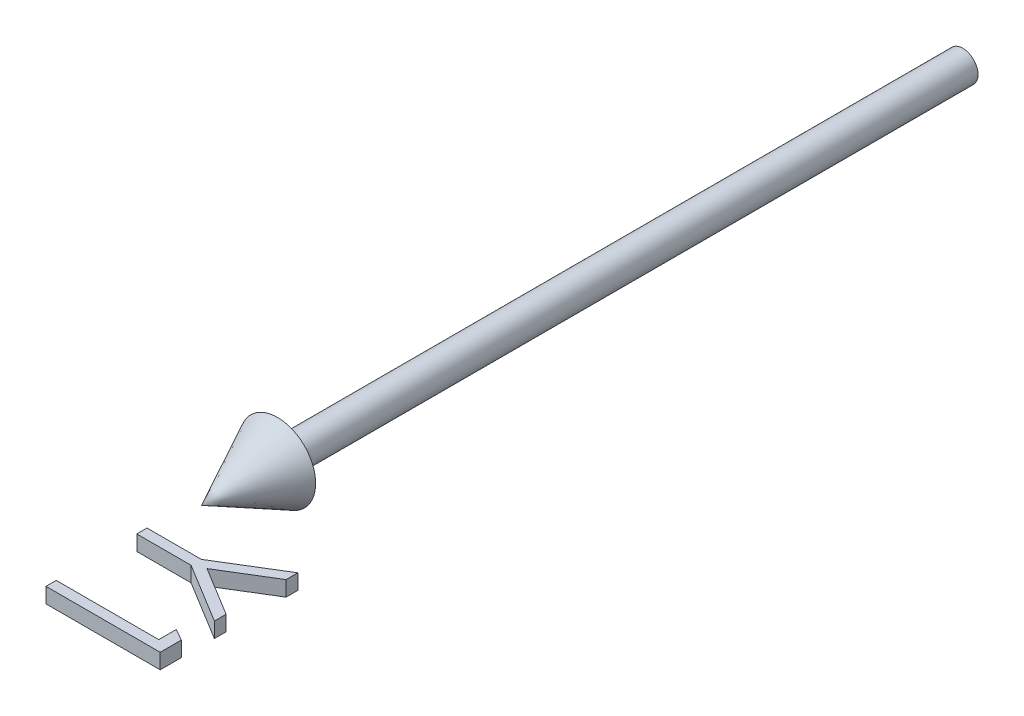
SolidWorks part; units mm, degrees
ref_plane "Front Plane" through (0, 0, 0) normal (0, 0, 1) x (1, 0, 0)
ref_plane "Top Plane" through (0, 0, 0) normal (0, 1, 0) x (1, 0, 0)
ref_plane "Right Plane" through (0, 0, 0) normal (1, 0, 0) x (0, 0, -1)
sketch "Sketch2" plane through (0, 0, 0) normal (0, 1, 0) x (1, 0, 0)
  line L0 (0, 41.95) -> (0, -114.4521) construction
  line L1 (-36.8894, 0) -> (41.4965, 0) construction
  line L2 (0, -100) -> (5, -90)
  line L3 (5, -90) -> (2, -90)
  line L4 (2, -90) -> (2, 0)
  line L5 (2, 0) -> (0, 0)
  line L6 (0, 0) -> (0, -100)
  dimension "D1" = 100
  dimension "D2" = 2
  dimension "D3" = 10
  dimension "D4" = 5
revolve "Revolve1" add sketch "Sketch2" angle 360 about L0
sketch "Sketch3" plane through (0, 0, 0) normal (0, 1, 0) x (1, 0, 0)
  line L0 (0, -101.5706) -> (0, -127.8138) construction
  text T0 "Y1" font "Century Gothic" height 15
extrude "Boss-Extrude1" add sketch "Sketch3" against normal blind 1 and the other way blind 1 separate body
equation "\"frame_arrow_length\"=100"
equation "\"D1@Sketch2\"=\"frame_arrow_length\""
equation "\"frame_arrow_odA\"=4"
equation "\"D2@Sketch2\"=\"frame_arrow_odA\"/2"
equation "\"frame_arrow_head_od\"=5"
equation "\"D4@Sketch2\"=\"frame_arrow_head_od\""
equation "\"frame_arrow_head_length\"=10"
equation "\"D3@Sketch2\"=\"frame_arrow_head_length\""
equation "\"tvarobot_theta1\"=30"
equation "\"link0_ringA_odA\"= 40"
equation "\"link0_ringA_odB\"= 25"
equation "\"link0_ringA_id\"= 20"
equation "\"link0_ringA_thickness\"= (\"link0_ringA_odB\" - \"link0_ringA_id\")/2"
equation "\"link0_ringA_height\"= 3"
equation "\"link0_ringA_heightA\"= 1.5"
equation "\"link0_ringA_heightB\"=\"link0_ringA_height\"-\"link0_ringA_heightA\""
equation "\"link0_ringB_odA\"= 40"
equation "\"link0_ringB_odB\"= 29"
equation "\"link0_ringB_id\"= \"link0_shaftA_bearing_id\"+1"
equation "\"link0_ringB_thickness\"= (\"link0_ringB_odB\" - \"link0_ringB_id\")/2"
equation "\"link0_ringB_height\"= 3"
equation "\"link0_ringB_heightA\"= 1.5"
equation "\"link0_ringB_heightB\"=\"link0_ringB_height\"-\"link0_ringB_heightA\""
equation "\"link0_shaftA_bearing_od\"=27"
equation "\"link0_shaftA_bearing_id\"=20"
equation "\"link0_shaftA_thrust_bearing_od\"=35"
equation "\"link0_shaftA_thrust_bearing_id\"=20.04"
equation "\"link0_shaftA_retaining_ring_id\"=18.5"
equation "\"link0_shaftA_retaining_ring_groove_width\"=1.5"
equation "\"link0_shaftA_spline_length\"=8.0"
equation "\"link0_shaftA_spline_depth\"=1.0"
equation "\"link0_shaftA_spline_width\"=4.0"
equation "\"link0_shaftA_odA\"=\"link0_shaftA_bearing_id\""
equation "\"link0_shaftA_odB\"=35"
equation "\"link0_shaftA_odC\"=\"link0_shaftA_bearing_id\""
equation "\"link0_shaftA_odD\"=\"link0_shaftA_odC\"-2*\"link0_shaftA_spline_depth\""
equation "\"link0_shaftA_odE\"=\"link0_shaftA_bearing_id\""
equation "\"link0_shaftA_odF\"=\"link0_shaftA_odE\"-2*\"link0_shaftA_spline_depth\""
equation "\"link0_shaftA_idA\"=10"
equation "\"link0_shaftA_idB\"=6"
equation "\"link0_shaftA_length\"=39.5"
equation "\"link0_shaftA_lengthA\"=8.0"
equation "\"link0_shaftA_lengthB\"=12.0"
equation "\"link0_shaftA_lengthC\"=35.0"
equation "\"link0_shaftA_lengthD\"=39.0"
equation "\"link0_shaftA_lengthE\"=\"link0_shaftA_length\"-\"link0_shaftA_lengthD\""
equation "\"link0_shaftA_offsetX\"=11"
equation "\"link0_shaftA_offsetY\"=0"
equation "\"link0_shaftA_bolt_pattern_dia\"=14"
equation "\"link0_motor_center_dist\"=26"
equation "\"link0_46t_pulley_spline_length\"=8"
equation "\"link0_46t_pulley_spline_depth\"=\"link0_shaftA_spline_depth\"*1.025"
equation "\"link0_46t_pulley_spline_width\"=\"link0_shaftA_spline_width\"*1.05"
equation "\"link0_46t_pulley_idA\"=\"link0_shaftA_bearing_id\"*1.025"
equation "\"link0_46t_pulley_idB\"=\"link0_46t_pulley_idA\"-2*\"link0_46t_pulley_spline_depth\""
equation "\"link0_shaftB_spline_length\"=10"
equation "\"link0_shaftB_spline_depth\"=1.0"
equation "\"link0_shaftB_spline_width\"=1.25"
equation "\"link0_shaftB_length\"=7"
equation "\"link0_shaftB_lengthA\"=1.5"
equation "\"link0_shaftB_lengthB\"=2.75"
equation "\"link0_shaftB_odA\"=32"
equation "\"link0_shaftB_odB\"=22"
equation "\"link0_shaftB_odC\"=20"
equation "\"link0_shaftB_idA\"=10"
equation "\"link0_shaftB_bolt_diameter\"=19"
equation "\"link0_shaftB_bearing_od\"=27"
equation "\"link0_shaftB_bearing_id\"=20"
equation "\"link0_motor_length\"=46.5"
equation "\"link0_motor_width\"=28.5"
equation "\"link0_motor_height\"=34"
equation "\"link0_motor_offset\"=8"
equation "\"link0_shellA_thickness\"=2.5"
equation "\"link0_shellB_thickness\"=\"link0_shellA_thickness\""
equation "\"link0_plateA_shellA_height\"=48"
equation "\"link0_shellA_width\" =\"link0_plateA_width\""
equation "\"link0_shellA_height\" = \"link0_plateA_shellA_height\"-\"link0_plateA_height\""
equation "\"link0_shellA_length\" = \"link0_plateA_lengthB\" "
equation "\"link0_shellB_length\"=\"link0_shellA_length\""
equation "\"link0_shellA_radius\" = 0.375*25.4"
equation "\"link0_shellA_radiusA\"= \"link0_plateA_radiusA\""
equation "\"link0_shellA_radiusB\"= \"link0_plateA_radiusB\""
equation "\"link0_shellA_radiusC\"= 3"
equation "\"link0_postA_height\"=7"
equation "\"link0_postA_width\"=16"
equation "\"link0_postA_length\"=20"
equation "\"link0_postA_posX\"=22"
equation "\"link0_postA_posY\"=17.5"
equation "\"link0_postA_pocket_width\"=6.0"
equation "\"link0_postA_pocket_length\"=2.5"
equation "\"link0_postA_pocket_depth\"=9"
equation "\"link0_postA_pocket_posZ\"=10"
equation "\"link0_postB_height\"=7"
equation "\"link0_postB_width\"=16"
equation "\"link0_postB_length\"=20"
equation "\"link0_postB_posX\"=22"
equation "\"link0_postB_posY\"=17.5"
equation "\"link0_postB_id\"=3.0"
equation "\"link0_postB_pocket_width\"=6.0"
equation "\"link0_postB_pocket_length\"=2.5"
equation "\"link0_postB_pocket_depth\"=9"
equation "\"link0_postB_pocket_posZ\"=10"
equation "\"link0_postC_height\"=7"
equation "\"link0_postC_width\"=16"
equation "\"link0_postC_length\"=20"
equation "\"link0_postC_posX\"=22"
equation "\"link0_postC_posY\"=17.5"
equation "\"link0_postC_id\"=3.0"
equation "\"link0_postC_pocket_width\"=6.0"
equation "\"link0_postC_pocket_length\"=2.5"
equation "\"link0_postC_pocket_depth\"=9"
equation "\"link0_postC_pocket_posZ\"=10"
equation "\"link0_postD_height\"=7"
equation "\"link0_postD_width\"=16"
equation "\"link0_postD_length\"=20"
equation "\"link0_postD_posX\"=22"
equation "\"link0_postD_posY\"=17.5"
equation "\"link0_postD_id\"=3.0"
equation "\"link0_postD_pocket_width\"=6.0"
equation "\"link0_postD_pocket_length\"=3.0"
equation "\"link0_postD_pocket_depth\"=9"
equation "\"link0_postD_pocket_posZ\"=10"
equation "\"link0_postE_height\"=5"
equation "\"link0_postE_width\"=16"
equation "\"link0_postE_length\"=\"link0_plateE_lengthA\"-\"link0_lip_height\""
equation "\"link0_postE_posZ\"=22"
equation "\"link0_postE_posX\"=17.5"
equation "\"link0_postE_posY\"=22"
equation "\"link0_postE_id\"=3.0"
equation "\"link0_postE_cbore_id\"=6.5"
equation "\"link0_postE_hole_id\"=3"
equation "\"link0_postF_posZ\"=22"
equation "\"link0_postF_posX\"=17.5"
equation "\"link0_postF_posY\"=\"link0_plateB_lengthA\"+4"
equation "\"link0_postF_id\"=3.0"
equation "\"link0_postF_cbore_id\"=6.5"
equation "\"link0_postF_hole_id\"=3"
equation "\"link0_postG_posZ\"=22"
equation "\"link0_postG_posX\"=17.5"
equation "\"link0_postG_posY\"=\"link0_plateB_lengthA\"+12"
equation "\"link0_postG_id\"=3.0"
equation "\"link0_postG_cbore_id\"=6.5"
equation "\"link0_postG_hole_id\"=3"
equation "\"link0_postHIJ_posY\"=6"
equation "\"link0_postH_posX\"=28"
equation "\"link0_postH_posY\"=20"
equation "\"link0_postH_posZ\"=20"
equation "\"link0_postH_length\"=10"
equation "\"link0_postI_posX\"=28"
equation "\"link0_postI_posY\"=20"
equation "\"link0_postI_posZ\"=135"
equation "\"link0_postI_length\"=10"
equation "\"link0_postJ_posX\"=28"
equation "\"link0_postJ_posY\"=20"
equation "\"link0_postJ_posZ\"=175"
equation "\"link0_postJ_length\"=10"
equation "\"link0_postK_posX\"=28"
equation "\"link0_postK_posY\"=20"
equation "\"link0_postK_posZ\"=175"
equation "\"link0_postK_length\"=10"
equation "\"link0_postL_posX\"=28"
equation "\"link0_postL_posY\"=20"
equation "\"link0_postL_posZ\"=135"
equation "\"link0_postL_length\"=10"
equation "\"link0_postM_posX\"=28"
equation "\"link0_postM_posY\"=20"
equation "\"link0_postM_posZ\"=35"
equation "\"link0_postM_length\"=10"
equation "\"link0_plateA_lengthA\"=30"
equation "\"link0_plateA_lengthB\"=150"
equation "\"link0_plateA_lengthC\"=30"
equation "\"link0_plateA_length\"=\"link0_plateA_lengthA\"+\"link0_plateA_lengthB\"+\"link0_plateA_lengthC\""
equation "\"link0_plateA_width\"=  68"
equation "\"link0_plateA_height\"= \"link0_plateA_radiusA\""
equation "\"link0_plateA_thickness\"=\"link0_shellA_thickness\""
equation "\"link0_plateA_radius\"= 9.5"
equation "\"link0_plateA_radiusA\"= 18"
equation "\"link0_plateA_radiusB\"= 18"
equation "\"link0_plateA_radiusC\"= 3"
equation "\"link0_plateB_length\"= 40"
equation "\"link0_plateB_width\"= \"link0_plateA_width\"*1.005"
equation "\"link0_plateB_height\"= \"link0_plateA_shellA_height\"*1.005"
equation "\"link0_plateB_lengthA\"=\"link0_lip_height\"+\"link0_plateD_thickness\"+\"link0_motor_mount_thickness\""
equation "\"link0_plateB_lengthB\"=\"link0_plateB_height\"-\"link0_plateB_lengthA\""
equation "\"link0_plateB_radiusA\"= \"link0_plateA_radiusA\""
equation "\"link0_plateB_radiusB\"= \"link0_plateA_radiusB\""
equation "\"link0_plateB_radiusC\"= 3"
equation "\"link0_plateB_idA\"=\"link0_shaftA_odC\"+1"
equation "\"link0_plateB_idB\"=\"link0_shaftA_bearing_od\"-2"
equation "\"link0_plateB_idC\"=\"link0_shaftA_bearing_od\"*1.005"
equation "\"link0_plateB_idD\"=\"link0_shaftA_thrust_bearing_od\"+1 "
equation "\"link0_plateB_depthA\"=1.0"
equation "\"link0_plateB_depthB\"=2.0"
equation "\"link0_plateB_depthC\"=8"
equation "\"link0_plateB_depthD\"=\"link0_plateB_length\"-\"link0_lip_height\"-\"link0_plateD_thickness\" "
equation "\"link0_plateC_length\"=\"link0_plateB_length\""
equation "\"link0_plateC_width\"= \"link0_plateB_width\""
equation "\"link0_plateC_height\"= .1*25.4"
equation "\"link0_plateA_hole_od\" = 0.1*25.4"
equation "\"link0_plateA_hole_delx\" = 0.5*25.4"
equation "\"link0_plateA_hole_delz\" = 0.75*25.4"
equation "\"link0_plateA_hole_offx\" = 0.0*25.4"
equation "\"link0_plateA_hole_offz\" = \"link0_plateA_length\"/2"
equation "\"link0_plateB_hole_od\" = 0.1*25.4"
equation "\"link0_plateB_hole_delx\"= 0.75*25.4"
equation "\"link0_plateB_hole_delz\"= 0.75*25.4"
equation "\"link0_plateB_hole_offx\"= 0.0*25.4"
equation "\"link0_plateB_hole_offz\"= 0.0*25.4"
equation "\"link0_plateC_hole_od\"= 0.1*25.4"
equation "\"link0_plateC_hole_delx\"= 0.75*25.4"
equation "\"link0_plateC_hole_delz\"= 0.75*25.4"
equation "\"link0_plateC_hole_offx\"= 0.0*25.4"
equation "\"link0_plateC_hole_offz\"= 0.0*25.4"
equation "\"link0_plateD_height\"=\"link0_plateB_height\"-2*\"link0_shellA_thickness\""
equation "\"link0_plateD_width\"=\"link0_plateB_width\"-2*\"link0_shellA_thickness\""
equation "\"link0_plateD_thickness\"=10"
equation "\"link0_plateD_radiusA\"=\"link0_plateB_radiusA\"-\"link0_shellA_thickness\""
equation "\"link0_plateD_odA\"= .375*25.4"
equation "\"link0_plateD_odB\"= .375*25.4"
equation "\"link0_plateD_bearing_id\"=20"
equation "\"link0_plateD_bearing_od\"=27"
equation "\"link0_plateE_radiusA\"=\"link0_plateA_radiusA\""
equation "\"link0_plateE_radiusB\"=\"link0_plateA_radiusB\""
equation "\"link0_plateE_radiusC\"=8.0"
equation "\"link0_plateE_length\"=30"
equation "\"link0_plateE_lengthA\"=16"
equation "\"link0_plateE_height\"=\"link0_plateB_height\""
equation "\"link0_plateE_width\"=\"link0_plateB_width\""
equation "\"link0_plateE_odA\"=\"gantry_coupler_id\"*0.99"
equation "\"link0_plateE_idA\"=\"link0_plateE_odA\"-20.0"
equation "\"link0_plateE_spline_depth\"=\"link0_poleA_spline_depth\"*1.05"
equation "\"link0_plateE_spline_width\"=\"link0_poleA_spline_width\"*1.075"
equation "\"link0_plateE_spline_length\"=\"link0_poleA_spline_length\""
equation "\"link0_plateE_coupler_length\"=46"
equation "\"link0_lip_height\"=5.0"
equation "\"link0_lip_thickness\"=2.0"
equation "\"link0_motor_mount_thickness\"=8.0"
equation "\"link0_motor_mount_idA\"=22"
equation "\"link0_motor_mount_idB\"=\"link0_shaftB_bearing_od\"*1.005"
equation "\"link0_motor_mount_idC\"=\"link0_shaftB_bearing_od\"-2"
equation "\"link0_motor_mount_depthA\"=5.5"
equation "\"link0_motor_mount_height\"=\"link0_plateD_height\""
equation "\"link0_motor_mount_width\"=\"link0_plateD_width\""
equation "\"link0_motor_mountL_height\"=36"
equation "\"link0_motor_mountL_heightA\"=12"
equation "\"link0_motor_mountL_length\"=50"
equation "\"link0_motor_mountL_lengthA\"=36"
equation "\"gantry_coupler_od\"=25.4*2.0"
equation "\"gantry_coupler_id\"=1.645*25.4"
equation "\"gantry_coupler_offsetX\"=\"link0_plateE_width\"/2"
equation "\"link0_poleA_odA\"=20"
equation "\"link0_poleA_odB\"=36"
equation "\"link0_poleA_idA\"=\"link0_poleA_odA\"-2*\"link0_poleA_thickness\""
equation "\"link0_poleA_idB\"=(\"link0_plateE_idA\"/2+1.5*\"link0_lip_thickness\")*1.04"
equation "\"link0_poleA_thickness\"=3.5"
equation "\"link0_poleA_length\"=100"
equation "\"link0_poleA_lengthA\"=18.5"
equation "\"link0_poleA_lengthB\"=80"
equation "\"link0_poleA_gasket_thickness\"=1.5"
equation "\"link0_poleA_spline_depth\"=1.0"
equation "\"link0_poleA_spline_width\"=4.0"
equation "\"link0_poleA_spline_length\"=10.0"
equation "\"link1_plateB_length\"=30"
equation "\"link1_lip_height\"=\"link0_lip_height\""
equation "\"link0_tension_plateA_width\"=12"
equation "\"link0_tension_plateA_lengthA\"=10.5"
equation "\"link0_tension_plateB_width\"=\"link0_tension_plateA_width\""
equation "\"link0_tension_plateB_lengthA\"=\"link0_tension_plateA_lengthA\""
equation "\"link0_tension_wheelA_posZ\"=7"
equation "\"link0_tension_wheelA_posX\"=\"link0_plateD_height\"/2-\"link0_tension_plateA_lengthA\""
equation "\"link0_m2_clear_hole_id\"=2.35"
equation "\"link0_m2_insert_hole_id\"=2.5"
equation "\"link0_m2_tap_hole_id\"=1.75"
equation "\"link0_m2_nut_socket_width\"=4.25"
equation "\"link0_m2_nut_socket_depth\"=2.5"
equation "\"link0_m2_cbore_id\"=3.75"
equation "\"link0_m2_cbore_depth\"=7"
equation "\"link0_m2_5_clear_hole_id\"=2.75"
equation "\"link0_m2_5_insert_hole_id\"=2.75"
equation "\"link0_m2_5_tap_hole_id\"=2.25"
equation "\"link0_m2_5_nut_socket_width\"=5.25"
equation "\"link0_m2_5_nut_socket_depth\"=2.5"
equation "\"link0_m2_5_cbore_id\"=4.75"
equation "\"link0_m2_5_cbore_depth\"=2.5"
equation "\"link0_m2_5_insert_access_length\"=6.0"
equation "\"link0_m2_5_insert_access_width\"=3.0"
equation "\"link0_m3_clear_hole_id\"=3.25"
equation "\"link0_m3_insert_hole_id\"=3"
equation "\"link0_m3_tap_hole_id\"=2.75"
equation "\"link0_m3_nut_socket_width\"=5.75"
equation "\"link0_m3_nut_socket_depth\"=4.0"
equation "\"link0_m3_cbore_id\"=5.75"
equation "\"link0_m3_cbore_depth\"=3.5"
equation "\"link0_m3_insert_access_length\"=4.5"
equation "\"link0_m3_insert_access_width\"=3.5"
equation "\"link0_rpi_mount_height\"=6"
equation "\"link0_rpi_mount_width\"=49"
equation "\"link0_rpi_mount_length\"=58"
equation "\"link0_rpi_mount_post_od\"=6"
equation "\"link0_rpi_mount_posZ\"=72"
equation "\"link0_rpi_mount_posX\"=11.5"
equation "\"link0_mcu_mount_height\"=5"
equation "\"link0_mcu_mount_width\"=49"
equation "\"link0_mcu_mount_length\"=58"
equation "\"link0_mcu_mount_post_od\"=6"
equation "\"link0_mcu_mount_posZ\"=164"
equation "\"link0_mcu_mount_posX\"=4"
equation "\"link0_pwr_mount_height\"=4"
equation "\"link0_pwr_mount_width\"=15.75"
equation "\"link0_pwr_mount_length\"=75.75"
equation "\"link0_pwr_mount_post_od\"=6"
equation "\"link0_pwr_mount_posZ\"=75"
equation "\"link0_pwr_mount_posX\"=16"
equation "\"link0_pwr_board_height\"=6"
equation "\"link0_pwr_board_width\"=21"
equation "\"link0_pwr_board_length\"=80"
